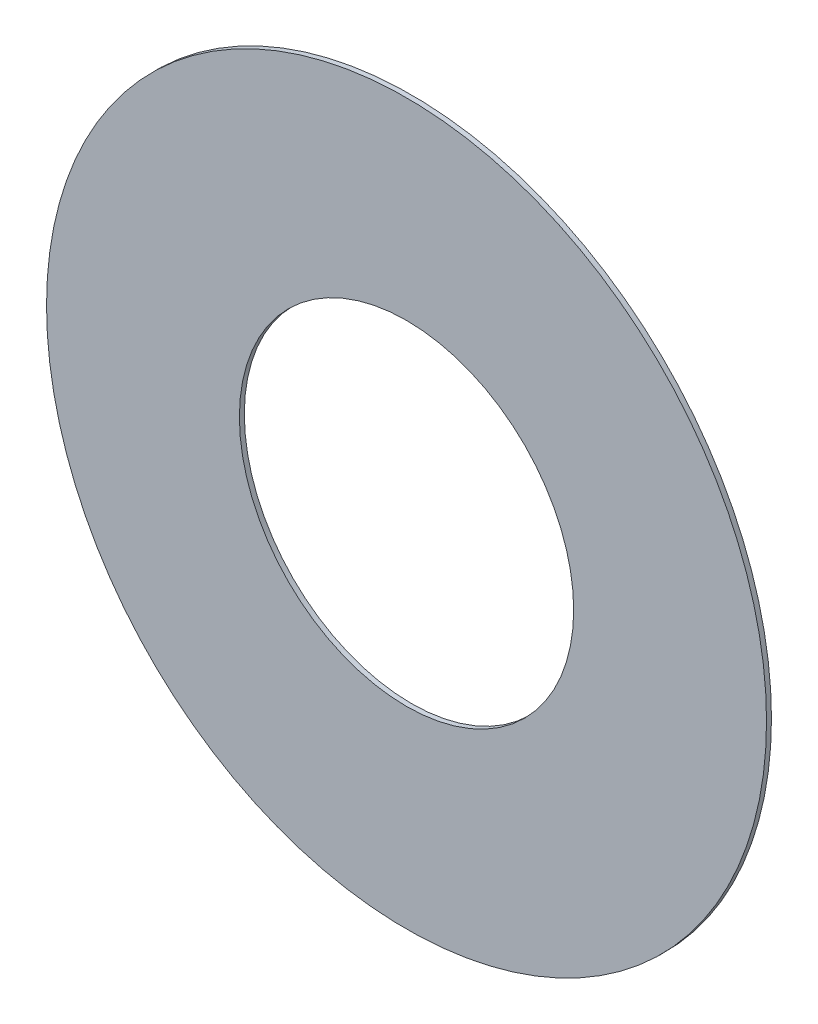
SolidWorks part; units mm, degrees
ref_plane "Front Plane" through (0, 0, 0) normal (0, 0, 1) x (1, 0, 0)
ref_plane "Top Plane" through (0, 0, 0) normal (0, 1, 0) x (1, 0, 0)
ref_plane "Right Plane" through (0, 0, 0) normal (1, 0, 0) x (0, 0, -1)
ref_plane "Plane1" through (0, 0, 0) normal (0, 0, -1) x (-1, 0, 0)
sketch "Sketch1" plane through (0, 0, 0) normal (0, 0, -1) x (-1, 0, 0)
  circle A0 centre (0, 0) radius 5.5563
  circle A1 centre (0, 0) radius 2.5797
extrude "Boss-Extrude1" add sketch "Sketch1" against normal blind 0.0762
ref_axis "Axis1" through (0, 0, 1.3892) along (0, 0, -1)
